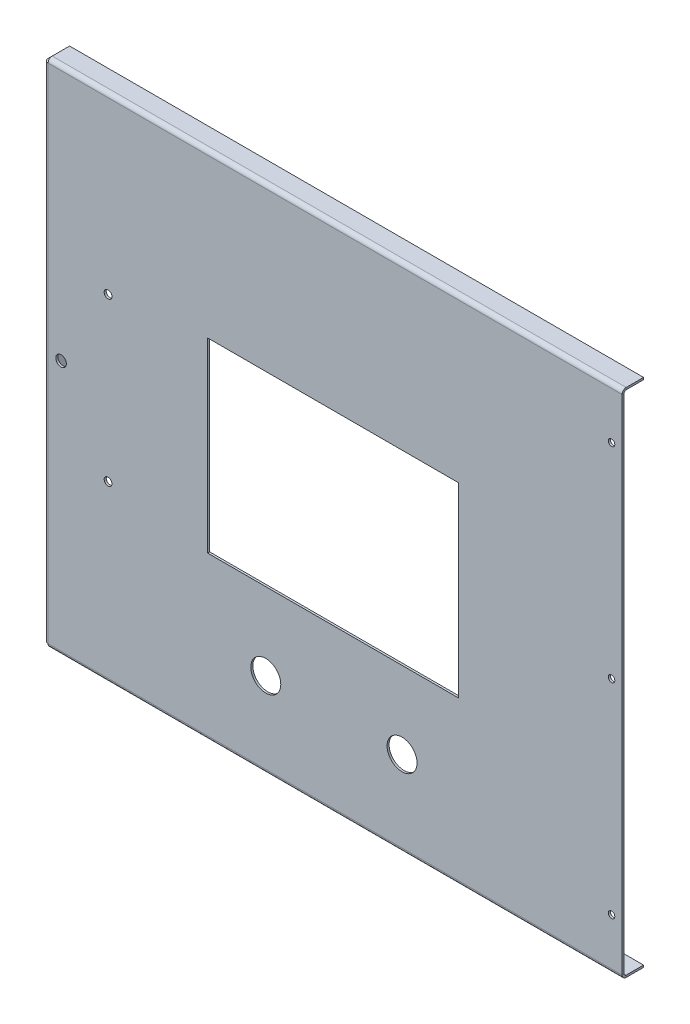
SolidWorks part; units mm, degrees
note: The reader was unsure of these and kept them because the rebuilt part matched: flange length of "Brida de arista1".
ref_plane "Alzado" through (0, 0, 0) normal (0, 0, 1) x (1, 0, 0)
ref_plane "Planta" through (0, 0, 0) normal (0, 1, 0) x (1, 0, 0)
ref_plane "Vista lateral" through (0, 0, 0) normal (1, 0, 0) x (0, 0, -1)
sketch "Croquis1" plane through (0, 0, 0) normal (0, 0, 1) x (1, 0, 0)
  line L1 (-215.519, -190.5) -> (215.519, -190.5)
  line L2 (-215.519, -190.5) -> (-215.519, 190.5)
  line L3 (-215.519, 190.5) -> (215.519, 190.5)
  line L4 (215.519, -190.5) -> (215.519, 190.5)
  line L5 (-215.519, -190.5) -> (215.519, 190.5) construction
  line L6 (-215.519, 190.5) -> (215.519, -190.5) construction
  point P0 (0, 0)
  dimension "D1" = 381
  dimension "D2" = 431.038
base flange "Brida base1" sketch "Croquis1" thickness 1.524 reverse thickness direction no parameters "D1"=1.524
sketch "Croquis6" plane through (0, 0, 0) normal (0, 0, 1) x (1, 0, 0)
  line L1 (-215.519, 190.5) -> (-212.471, 190.5)
  line L2 (-215.519, 190.5) -> (-215.519, 187.452)
  line L3 (-215.519, 187.452) -> (-212.471, 187.452)
  line L4 (-212.471, 190.5) -> (-212.471, 187.452)
  line L5 (-215.519, -190.5) -> (-212.471, -190.5)
  line L6 (-215.519, -190.5) -> (-215.519, -187.452)
  line L7 (-215.519, -187.452) -> (-212.471, -187.452)
  line L8 (-212.471, -190.5) -> (-212.471, -187.452)
  dimension "D1" = 3.048
  dimension "D2" = 3.048
extrude "Cortar-Extruir1" cut sketch "Croquis6" against normal through all normal cut yes
edge flange "Brida de arista1" sketch "Croquis13" flange profiles "Croquis13", "Croquis14", "Croquis15" flange angle 90 flange length 16.002 flange position material inside bend radius 1.524 thickness 1.524 relief rectangular gap distance 1 parameters "D6"=10, "D8"=1
sketch "Croquis13" plane through (0, 190.5, -1.524) normal (0, -1, 0) x (-1, 0, 0)
  line L2 (-215.519, 0) -> (-215.519, 14.478)
  line L3 (-215.519, 14.478) -> (212.471, 14.478)
  line L4 (212.471, 14.478) -> (212.471, 0)
  line L5 (212.471, 0) -> (-215.519, 0) construction
  line L6 (212.471, 0) -> (-215.519, 0)
sketch "Croquis14" plane through (-215.519, 0, -1.524) normal (1, 0, 0) x (0, -1, 0)
  line L0 (187.452, 0) -> (-187.452, 0) construction
  line L1 (187.452, 0) -> (-187.452, 0)
  line L2 (187.452, 0) -> (187.452, 14.478)
  line L3 (187.452, 14.478) -> (-187.452, 14.478)
  line L4 (-187.452, 14.478) -> (-187.452, 0)
sketch "Croquis15" plane through (0, -190.5, -1.524) normal (0, 1, 0) x (1, 0, 0)
  line L0 (215.519, 0) -> (-212.471, 0) construction
  line L1 (215.519, 0) -> (-212.471, 0)
  line L2 (215.519, 0) -> (215.519, 14.478)
  line L3 (215.519, 14.478) -> (-212.471, 14.478)
  line L4 (-212.471, 14.478) -> (-212.471, 0)
bend "Pliegue de arista1" bend radius 1.524 bend angle 90 parameters "D5"=1
bend "Pliegue de arista2" bend radius 1.524 bend angle 90 parameters "D5"=2
bend "Pliegue de arista3" bend radius 1.524 bend angle 90 parameters "D5"=3
sketch "Croquis16" plane through (0, 0, 0) normal (0, 0, 1) x (1, 0, 0)
  line L0 (-212.471, -190.5) -> (215.519, -190.5) construction
  line L5 (-212.471, 190.5) -> (215.519, 190.5) construction
  line L6 (215.519, -187.452) -> (215.519, 187.452) construction
  line L7 (-93.599, -69.469) -> (93.345, -69.469)
  line L8 (-93.599, -69.469) -> (-93.599, 69.469)
  line L9 (-93.599, 69.469) -> (93.345, 69.469)
  line L10 (93.345, -69.469) -> (93.345, 69.469)
  line L11 (-93.599, -69.469) -> (93.345, 69.469) construction
  line L12 (-93.599, 69.469) -> (93.345, -69.469) construction
  circle A0 centre (-202.819, 0) radius 3.9624
  circle A1 centre (-167.767, 60.452) radius 2.8956
  circle A2 centre (-167.767, -60.452) radius 2.8956
  circle A3 centre (-50.165, -127) radius 11.176
  circle A4 centre (51.435, -127) radius 11.176
  circle A5 centre (207.645, 152.4) radius 2.413
  circle A6 centre (207.645, 0) radius 2.413
  circle A7 centre (207.645, -152.4) radius 2.413
  point P0 (-0.127, 0)
  dimension "D8" = 101.6
  dimension "D10" = 60.452
  dimension "D11" = 60.452
  dimension "D14" = 4.826
  dimension "D15" = 22.352
  dimension "D16" = 7.9248
  dimension "D17" = 5.7912
  dimension "D1" = 38.1
  dimension "D2" = 38.1
  dimension "D3" = 7.874
  dimension "D4" = 215.646
  dimension "D5" = 383.286
  dimension "D6" = 418.338
  dimension "D7" = 164.084
  dimension "D9" = 317.5
  dimension "D12" = 138.938
  dimension "D13" = 186.944
extrude "Cortar-Extruir2" cut sketch "Croquis16" against normal through all normal cut yes
sketch "Líneas de pliegue1" [suppressed] plane through (0, 0, 0) normal (0, 1, 0) x (1, 0, 0)
sketch "Cuadro delimitador1" [suppressed] plane through (0, 0, 0) normal (0, 1, 0) x (1, 0, 0)
sheet metal parameters "Chapa metálica1" thickness 1.524 parameters "D1"=2.667
flat pattern "Chapa desplegada1" [suppressed]
sketch "Líneas de pliegue2" plane through (0, 0, 0) normal (0, 1, 0) x (1, 0, 0)
sketch3d "Cuadro delimitador2" [suppressed]
  line L0 (-215.519, -190.5, 0) -> (215.519, -190.5, 0) construction
  line L1 (-215.519, 190.5, 0) -> (215.519, 190.5, 0) construction
  line L2 (-215.519, -190.5, 0) -> (-215.519, 190.5, 0) construction
  line L3 (215.519, -190.5, 0) -> (215.519, 190.5, 0) construction
sheet metal parameters "Chapa metálica2" thickness 1.524 parameters "D1"=2.667
flat pattern "Chapa desplegada1"
sketch "Líneas de pliegue2" plane through (0, 0, 0) normal (0, 1, 0) x (1, 0, 0)
sketch3d "Cuadro delimitador2" [suppressed]
  line L0 (-215.519, -190.5, 0) -> (215.519, -190.5, 0) construction
  line L1 (-215.519, 190.5, 0) -> (215.519, 190.5, 0) construction
  line L2 (-215.519, -190.5, 0) -> (-215.519, 190.5, 0) construction
  line L3 (215.519, -190.5, 0) -> (215.519, 190.5, 0) construction
sheet metal parameters "Chapa metálica3" thickness 1.524 parameters "D1"=2.667
flat pattern "Chapa desplegada1"
sketch "Líneas de pliegue2" plane through (0, 0, 0) normal (0, 0, 1) x (1, 0, 0)
  line L0 (-212.471, -189.2235) -> (215.519, -189.2235) construction
  line L1 (-214.2425, 187.452) -> (-214.2425, -187.452) construction
  line L2 (215.519, 189.2235) -> (-212.471, 189.2235) construction
  line L3 (-212.471, -189.2235) -> (215.519, -189.2235) construction
  line L4 (-214.2425, 187.452) -> (-214.2425, -187.452) construction
  line L5 (215.519, 189.2235) -> (-212.471, 189.2235) construction
sketch3d "Cuadro delimitador2" [suppressed]
  line L0 (-228.968, -203.949, 0) -> (215.519, -203.949, 0) construction
  line L1 (-228.968, 203.949, 0) -> (215.519, 203.949, 0) construction
  line L2 (-228.968, -203.949, 0) -> (-228.968, 203.949, 0) construction
  line L3 (215.519, -203.949, 0) -> (215.519, 203.949, 0) construction
bend of the flat pattern "Aplanar-<Pliegue de arista1>1"
bend of the flat pattern "Aplanar-<Pliegue de arista2>1"
bend of the flat pattern "Aplanar-<Pliegue de arista3>1"
sheet metal parameters "Chapa metálica4" thickness 1.524 parameters "D1"=2.667
flat pattern "Chapa desplegada1"
sketch "Líneas de pliegue2" plane through (0, 0, 0) normal (0, 0, 1) x (1, 0, 0)
  line L0 (-212.471, -189.2235) -> (215.519, -189.2235) construction
  line L1 (-214.2425, 187.452) -> (-214.2425, -187.452) construction
  line L2 (215.519, 189.2235) -> (-212.471, 189.2235) construction
  line L3 (-212.471, -189.2235) -> (215.519, -189.2235) construction
  line L4 (-214.2425, 187.452) -> (-214.2425, -187.452) construction
  line L5 (215.519, 189.2235) -> (-212.471, 189.2235) construction
sketch3d "Cuadro delimitador2" [suppressed]
  line L0 (-228.968, -203.949, 0) -> (215.519, -203.949, 0) construction
  line L1 (-228.968, 203.949, 0) -> (215.519, 203.949, 0) construction
  line L2 (-228.968, -203.949, 0) -> (-228.968, 203.949, 0) construction
  line L3 (215.519, -203.949, 0) -> (215.519, 203.949, 0) construction
bend of the flat pattern "Aplanar-<Pliegue de arista1>1"
bend of the flat pattern "Aplanar-<Pliegue de arista2>1"
bend of the flat pattern "Aplanar-<Pliegue de arista3>1"
